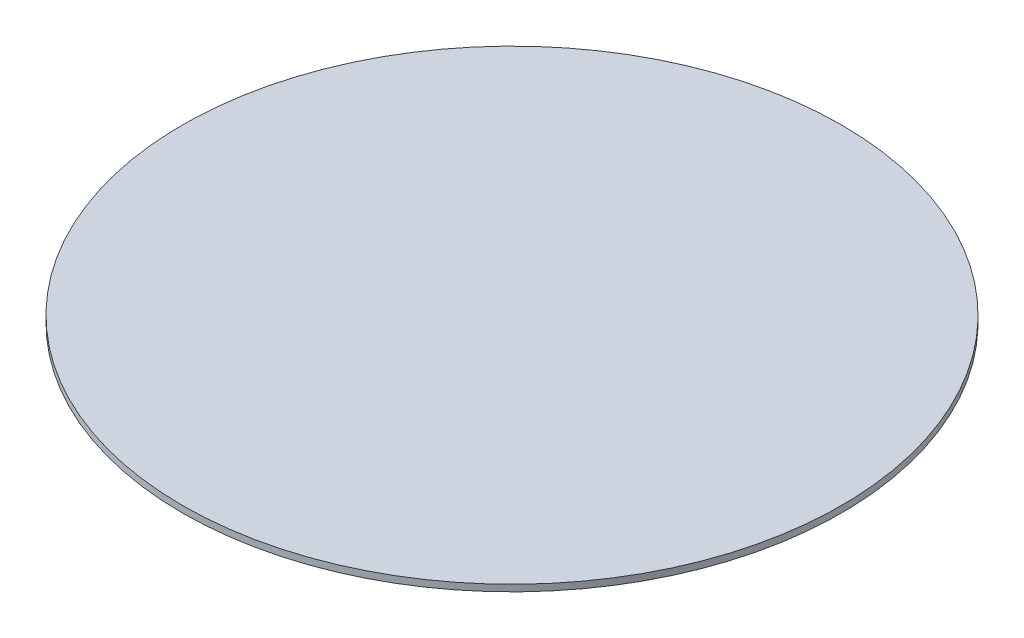
SolidWorks part; units mm, degrees
ref_plane "Front Plane" through (0, 0, 0) normal (0, 0, 1) x (1, 0, 0)
ref_plane "Top Plane" through (0, 0, 0) normal (0, 1, 0) x (1, 0, 0)
ref_plane "Right Plane" through (0, 0, 0) normal (1, 0, 0) x (0, 0, -1)
ref_axis "Axis1" through (0, -55, 0) along (0, 1, 0)
sketch "Sketch1" plane through (0, 0, 0) normal (0, 1, 0) x (1, 0, 0)
  circle A0 centre (0, 0) radius 500
extrude "Boss-Extrude1" add sketch "Sketch1" along normal blind 10 contours A0
